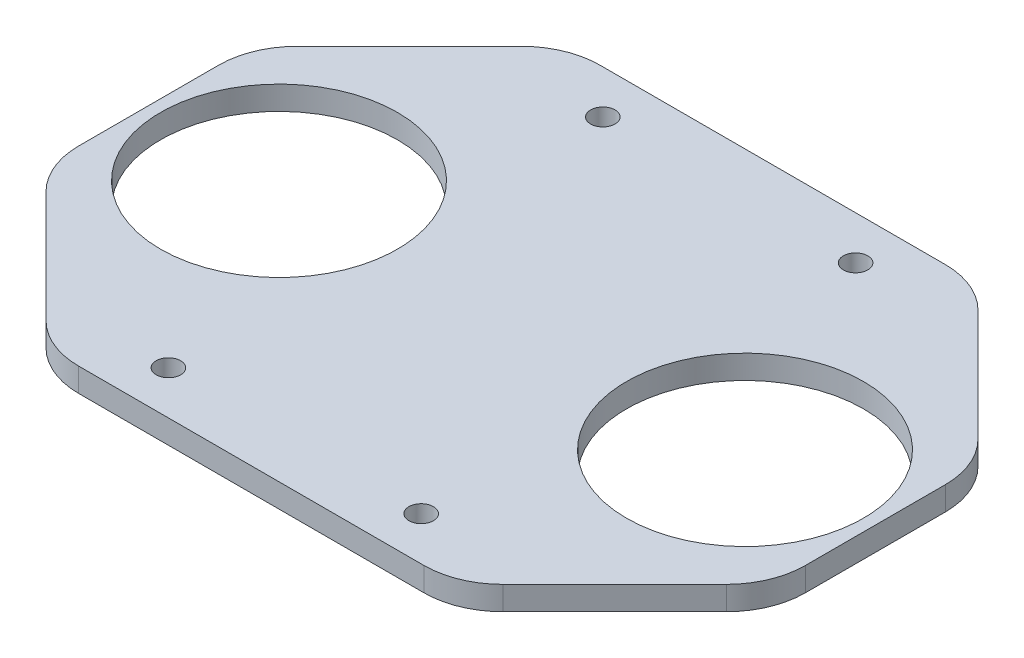
SolidWorks part; units mm, degrees
material "Thornel Mat VMA"
ref_plane "前视基准面" through (0, 0, 0) normal (0, 0, 1) x (1, 0, 0)
ref_plane "上视基准面" through (0, 0, 0) normal (0, 1, 0) x (1, 0, 0)
ref_plane "右视基准面" through (0, 0, 0) normal (1, 0, 0) x (0, 0, -1)
sketch "草图1" plane through (0, 0, 0) normal (0, 1, 0) x (1, 0, 0)
  line L1 (-16, 27.5) -> (16, 27.5) construction
  line L2 (-16, 27.5) -> (-16, -27.5) construction
  line L3 (-16, -27.5) -> (16, -27.5) construction
  line L4 (16, 27.5) -> (16, -27.5) construction
  line L5 (-16, 27.5) -> (16, -27.5) construction
  line L6 (-16, -27.5) -> (16, 27.5) construction
  line L7 (-46, 33) -> (46, 33)
  line L8 (-46, 33) -> (-46, -33)
  line L9 (-46, -33) -> (46, -33)
  line L10 (46, 33) -> (46, -33)
  line L11 (-46, 33) -> (46, -33) construction
  line L12 (-46, -33) -> (46, 33) construction
  circle A0 centre (-16, 27.5) radius 1.55
  circle A1 centre (16, 27.5) radius 1.55
  circle A2 centre (16, -27.5) radius 1.55
  circle A3 centre (-16, -27.5) radius 1.55
  point P0 (0, 0)
  point P10 (0, 0)
  dimension "D3" = 3.1
  dimension "D4" = 3.1
  dimension "D5" = 3.1
  dimension "D6" = 3.1
  dimension "D1" = 55
  dimension "D2" = 32
  dimension "D7" = 66
  dimension "D8" = 92
extrude "凸台-拉伸1" add sketch "草图1" along normal blind 3
chamfer "倒角1" distance 20 angle 45 4 edges at (-46, 1.5, 33) (46, 1.5, 33) (46, 1.5, -33) (-46, 1.5, -33)
sketch "草图3" plane through (0, 3, 0) normal (0, 1, 0) x (1, 0, 0)
  line L0 (0, 0) -> (0, 21.4113) construction
  line L1 (-29.5, 21.3564) -> (-29.5, -21.3564) construction
  line L2 (-29.5, 0) -> (-32.6058, -11.5911) construction
  line L3 (-29.5, 0) -> (-32.6058, 11.5911) construction
  line L4 (29.5, 0) -> (32.6058, 11.5911) construction
  line L5 (29.5, 0) -> (32.6058, -11.5911) construction
  circle A1 centre (-29.5, 0) radius 2.9 construction
  circle A3 centre (-29.5, 0) radius 2.9 construction
  circle A4 centre (-29.5, 0) radius 15
  circle A5 centre (29.5, 0) radius 2.9 construction
  circle A6 centre (29.5, 0) radius 15
  circle A17 centre (29.5, 0) radius 2.9 construction
  circle A18 centre (29.5, 0) radius 15
  point P20 (-29.5, 0)
  dimension "D1" = 30
  dimension "D4" = 15
  dimension "D5" = 15
extrude "切除-拉伸1" cut sketch "草图3" against normal through all and the other way through all contours A4 | A6 region at (-29.5, 3, 0) region at (29.5, 3, 0)
fillet "圆角1" radius 10 8 edges at (26, 1.5, -33) (46, 1.5, -13) (46, 1.5, 13) (26, 1.5, 33) (-26, 1.5, 33) (-46, 1.5, 13) (-46, 1.5, -13) (-26, 1.5, -33)
